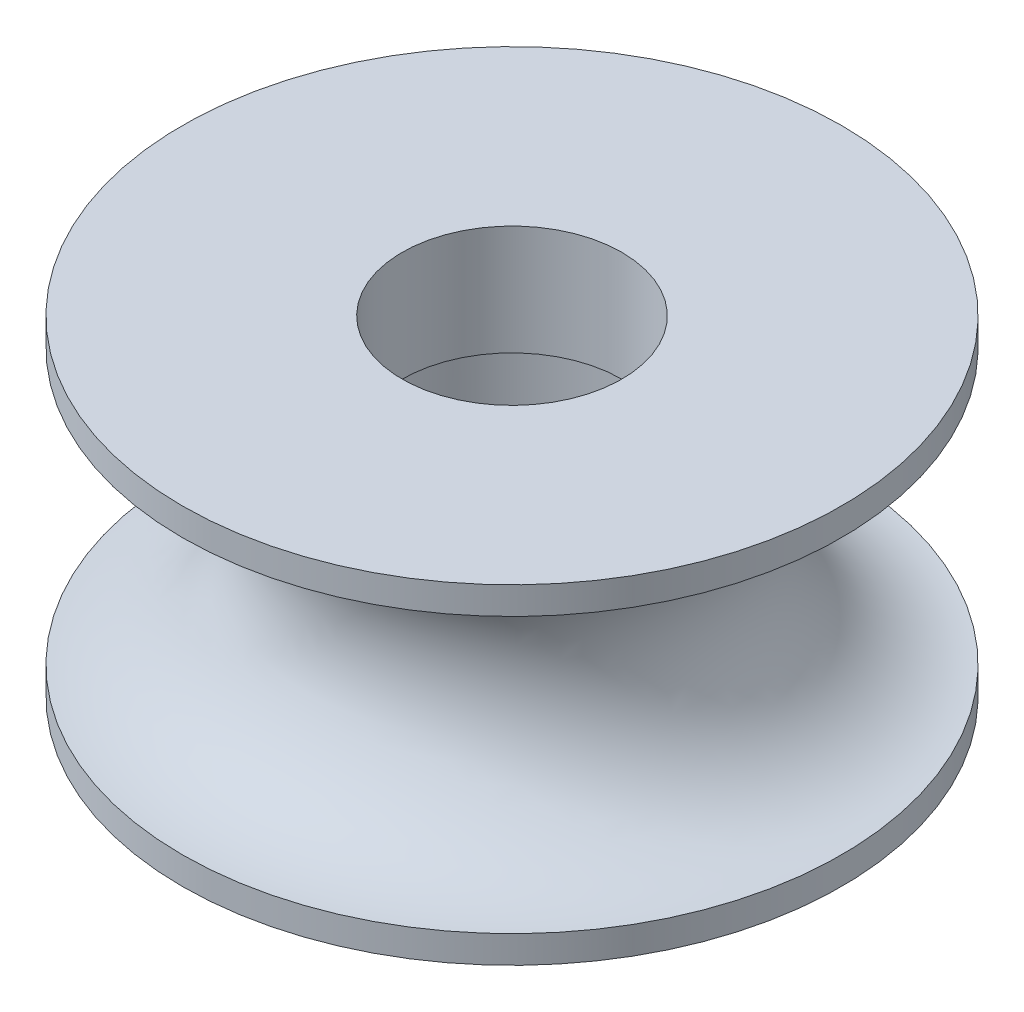
SolidWorks part; units mm, degrees
ref_plane "前视基准面" through (0, 0, 0) normal (0, 0, 1) x (1, 0, 0)
ref_plane "上视基准面" through (0, 0, 0) normal (0, 1, 0) x (1, 0, 0)
ref_plane "右视基准面" through (0, 0, 0) normal (1, 0, 0) x (0, 0, -1)
sketch "草图6" plane through (0, 0, 0) normal (0, 0, 1) x (1, 0, 0)
  line L0 (0, 0) -> (0, 17.1768) construction
sketch "草图7" plane through (0, 0, 0) normal (0, 0, 1) x (1, 0, 0)
  line L1 (-5, 5) -> (-5, -5)
  line L3 (0, -200000) -> (0, 200017.1768) construction
  line L4 (0, 0) -> (-53.5124, 0) construction
  line L5 (-12, 5) -> (-12, 0) construction
  line L6 (-12, 0) -> (-12, -5) construction
  line L7 (-12, 0) -> (-12, 5) construction
  line L8 (-12, 5) -> (-12, 6)
  line L9 (-12, 6) -> (-5, 6)
  line L10 (-5, 6) -> (-5, 5)
  line L11 (-12, -5) -> (-12, -6)
  line L12 (-12, -6) -> (-5, -6)
  line L13 (-5, -6) -> (-5, -5)
  circle A0 centre (-12, 0) radius 5 construction
  arc A1 (-12, 5) -> (-12, -5) centre (-12, 0) cw
  point P6 (-5, 0)
  dimension "D1" = 5
  dimension "D2" = 5
  dimension "D3" = 1
  dimension "D4" = 7
  dimension "D5" = 180
  dimension "D6" = 1
revolve "旋转1" add sketch "草图7" angle 360 about L0
sketch "草图8" plane through (0, 0, 0) normal (0, 1, 0) x (1, 0, 0)
  line L0 (0, 12) -> (0, -12) construction
  circle A0 centre (0, 0) radius 12 construction
sketch "草图9" plane through (0, 0, 0) normal (0, 0, 1) x (1, 0, 0)
  line L0 (-5, -6) -> (5, -6) construction
  line L1 (-5, 6) -> (-4, 6)
  line L2 (-5, 6) -> (-5, 2)
  line L3 (-5, -6) -> (-4, -6)
  line L4 (-4, 6) -> (-4, 2)
  line L5 (-5, 2) -> (-4, 2)
  line L6 (-5, -2) -> (-4, -2)
  line L7 (-5, -2) -> (-5, -6)
  line L8 (-4, -2) -> (-4, -6)
  dimension "D1" = 1
  dimension "D2" = 4
  dimension "D3" = 4
revolve "旋转2" add sketch "草图9" angle 360 about L0
